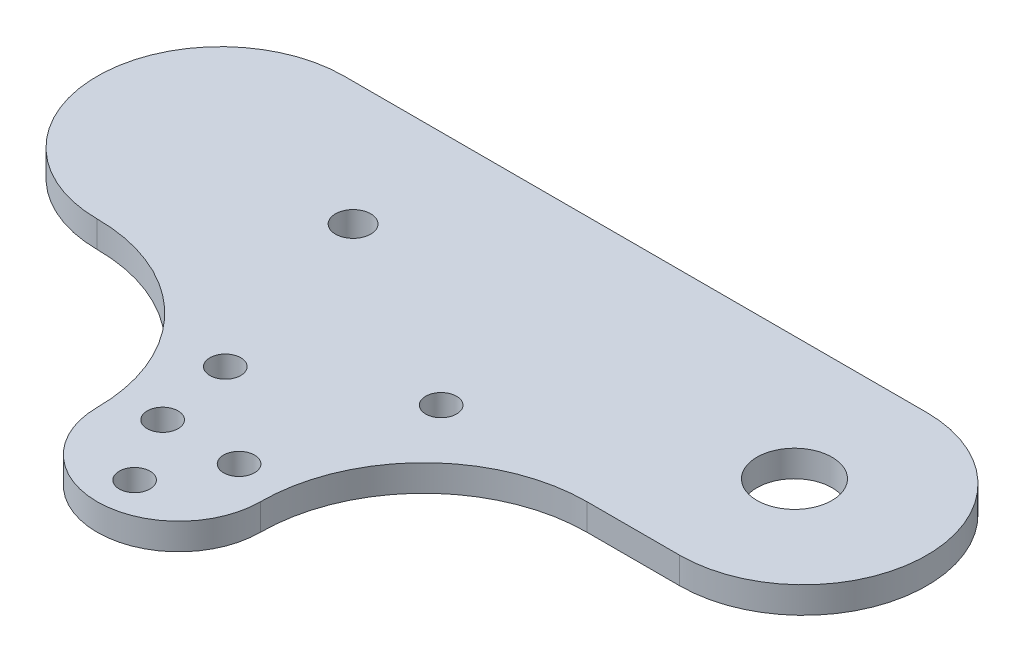
SolidWorks part; units mm, degrees
ref_plane "前视" through (0, 0, 0) normal (0, 0, 1) x (1, 0, 0)
ref_plane "上视" through (0, 0, 0) normal (0, 1, 0) x (1, 0, 0)
ref_plane "右视" through (0, 0, 0) normal (1, 0, 0) x (0, 0, -1)
sketch "草图1" plane through (0, 0, 0) normal (0, 1, 0) x (1, 0, 0)
  line L1 (-40, 14) -> (40, 14)
  line L2 (-40, 14) -> (-40, -14)
  line L3 (-40, -14) -> (40, -14)
  line L4 (40, 14) -> (40, -14)
  line L5 (-40, 14) -> (40, -14) construction
  line L6 (-40, -14) -> (40, 14) construction
  circle A0 centre (25, 0) radius 4.25
  circle A1 centre (-25, 0) radius 2
  point P0 (0, 0)
  dimension "D3" = 4
  dimension "D4" = 8.5
  dimension "D1" = 80
  dimension "D2" = 28
  dimension "D5" = 50
  dimension "D6" = 15
extrude "凸台-拉伸1" add sketch "草图1" along normal blind 3
sketch "草图2" plane through (0, 3, 0) normal (0, 1, 0) x (1, 0, 0)
  text T0 "        <b>     1</b>"
extrude "凸台-拉伸2" [suppressed] add sketch "草图2" along normal blind 0.5
fillet "圆角2" 2 edges at (40, 1.5, -14) (40, 1.5, 14) type full round first side face at (0, 1.5, -14) second side face at (0, 1.5, 14) middle face at (40, 1.5, 0)
sketch "草图4" plane through (0, 0, 0) normal (0, -1, 0) x (1, 0, 0)
  line L0 (-40, -14) -> (-40, 14) construction
  line L1 (-40, 14) -> (-40, -14)
  arc A0 (-40, 14) -> (-40, -14) centre (-40, 0) ccw
extrude "凸台-拉伸3" add sketch "草图4" against normal blind 3
sketch "草图5" plane through (0, 0, 0) normal (0, -1, 0) x (-1, 0, 0)
  line L0 (40, -14) -> (-26, -14) construction
  line L1 (21.5, -14) -> (3, -14)
  line L2 (21.5, -14) -> (21.5, -32.5)
  line L3 (21.5, -32.5) -> (3, -32.5)
  line L4 (3, -14) -> (3, -32.5)
  dimension "D1" = 18.5
  dimension "D2" = 18.5
  dimension "D3" = 18.5
extrude "凸台-拉伸4" add sketch "草图5" against normal blind 3
fillet "圆角3" radius 18.5 2 edges at (-21.5, 1.5, 14) (-3, 1.5, 14)
sketch "草图6" plane through (0, 0, 0) normal (0, -1, 0) x (1, 0, 0)
  line L0 (-3, 32.5) -> (-21.5, 32.5) construction
  line L1 (-21.5, 32.5) -> (-3, 32.5)
  arc A0 (-3, 32.5) -> (-21.5, 32.5) centre (-12.25, 32.5) ccw
extrude "凸台-拉伸5" add sketch "草图6" against normal blind 3
sketch "草图10" plane through (0, 0, 0) normal (0, -1, 0) x (1, 0, 0)
  circle A0 centre (-12.25, 32.5) radius 5 construction
  circle A1 centre (-12.25, 37.5) radius 1.75
  circle A2 centre (-7.9199, 30) radius 1.75
  circle A3 centre (-16.5801, 30) radius 1.75
  circle A4 centre (-18.2441, 21.2337) radius 1.75
  circle A5 centre (-2.2404, 12.786) radius 1.75
  circle A6 centre (-12.25, 32.5) radius 5 construction
  point P11 (-11.9645, 24.0861)
  point P13 (-12.25, 32.5)
  point P17 (-12.25, 37.5)
  dimension "D1" = 10
  dimension "D2" = 3.5
  dimension "D3" = 3.5
  dimension "D4" = 3.5
  dimension "D5" = 10
extrude "切除-拉伸1" cut sketch "草图10" against normal up to next
